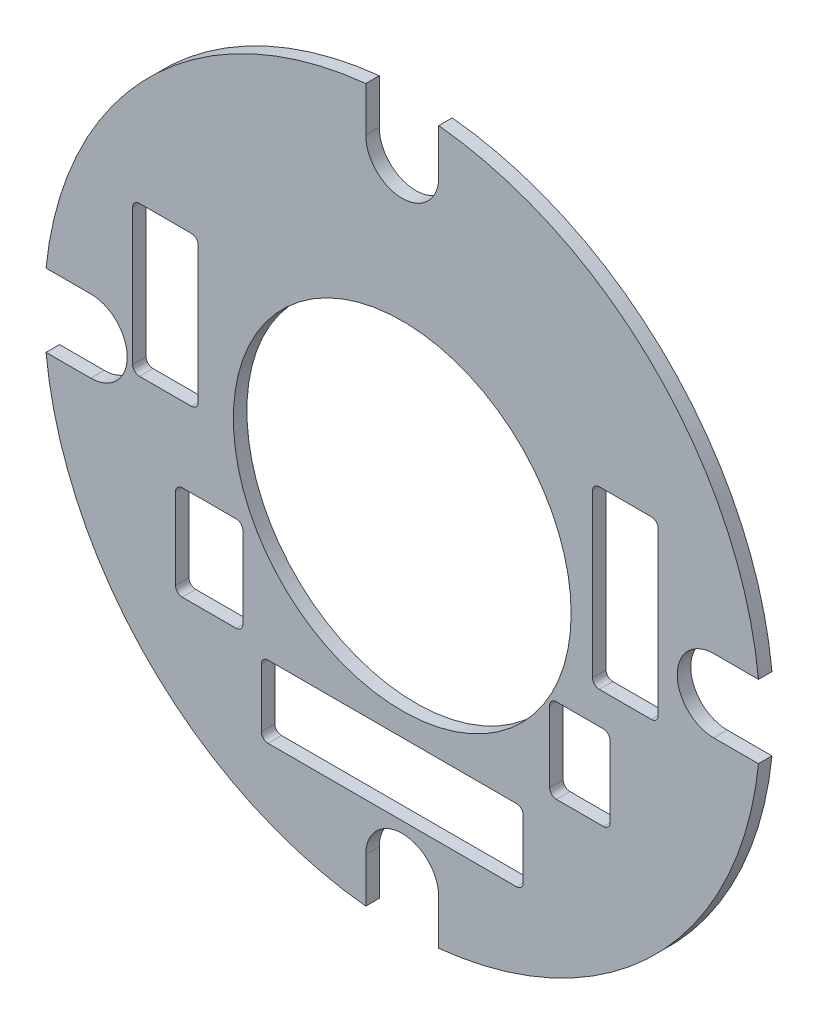
SolidWorks part; units mm, degrees
material "POM 乙缩醛共聚物"
ref_plane "前视基准面" through (0, 0, 0) normal (0, 0, 1) x (1, 0, 0)
ref_plane "上视基准面" through (0, 0, 0) normal (0, 1, 0) x (1, 0, 0)
ref_plane "右视基准面" through (0, 0, 0) normal (1, 0, 0) x (0, 0, -1)
sketch "草图1" plane through (0, 0, 0) normal (0, 0, 1) x (1, 0, 0)
  circle A0 centre (0, 0) radius 12.5
  circle A1 centre (0, 0) radius 26.5
extrude "凸台-拉伸1" add sketch "草图1" along normal blind 1
sketch "草图2" plane through (22.804, -9.3503, -2.5) normal (0, 0, 1) x (1, 0, 0)
  line L0 (-38.402, 19.6523) -> (-42.258, 19.6523)
  line L25 (-42.758, 19.1523) -> (-42.758, 9.0733)
  line L26 (-38.402, 8.5733) -> (-42.258, 8.5733)
  line L27 (-37.902, 19.1523) -> (-37.902, 9.0733)
  line L28 (-8.222, 18.5093) -> (-4.366, 18.5093)
  line L29 (-3.866, 18.0093) -> (-3.866, 6.0253)
  line L30 (-8.222, 5.5253) -> (-4.366, 5.5253)
  line L31 (-8.722, 18.0093) -> (-8.722, 6.0253)
  line L36 (-32.733, -4.8587) -> (-14.352, -4.8587)
  line L37 (-13.852, -5.3587) -> (-13.852, -9.6907)
  line L38 (-32.733, -10.1907) -> (-14.352, -10.1907)
  line L39 (-33.233, -5.3587) -> (-33.233, -9.6907)
  line L40 (-35.1, 3.0153) -> (-39.083, 3.0153)
  line L41 (-39.583, 2.5153) -> (-39.583, -3.4997)
  line L42 (-35.1, -3.9997) -> (-39.083, -3.9997)
  line L43 (-34.6, 2.5153) -> (-34.6, -3.4997)
  line L44 (-11.397, 3.1423) -> (-7.922, 3.1423)
  line L45 (-7.422, 2.6423) -> (-7.422, -2.6107)
  line L46 (-11.397, -3.1107) -> (-7.922, -3.1107)
  line L47 (-11.897, 2.6423) -> (-11.897, -2.6107)
  arc A0 (-38.402, 19.6523) -> (-37.902, 19.1523) centre (-38.402, 19.1523) cw
  arc A1 (-42.258, 19.6523) -> (-42.758, 19.1523) centre (-42.258, 19.1523) ccw
  arc A2 (-42.758, 9.0733) -> (-42.258, 8.5733) centre (-42.258, 9.0733) ccw
  arc A3 (-38.402, 8.5733) -> (-37.902, 9.0733) centre (-38.402, 9.0733) ccw
  arc A4 (-39.583, -3.4997) -> (-39.083, -3.9997) centre (-39.083, -3.4997) ccw
  arc A5 (-39.083, 3.0153) -> (-39.583, 2.5153) centre (-39.083, 2.5153) ccw
  arc A6 (-35.1, 3.0153) -> (-34.6, 2.5153) centre (-35.1, 2.5153) cw
  arc A7 (-35.1, -3.9997) -> (-34.6, -3.4997) centre (-35.1, -3.4997) ccw
  arc A8 (-32.733, -4.8587) -> (-33.233, -5.3587) centre (-32.733, -5.3587) ccw
  arc A9 (-32.733, -10.1907) -> (-33.233, -9.6907) centre (-32.733, -9.6907) cw
  arc A10 (-13.852, -9.6907) -> (-14.352, -10.1907) centre (-14.352, -9.6907) cw
  arc A11 (-14.352, -4.8587) -> (-13.852, -5.3587) centre (-14.352, -5.3587) cw
  arc A12 (-7.422, -2.6107) -> (-7.922, -3.1107) centre (-7.922, -2.6107) cw
  arc A13 (-11.397, -3.1107) -> (-11.897, -2.6107) centre (-11.397, -2.6107) cw
  arc A14 (-11.397, 3.1423) -> (-11.897, 2.6423) centre (-11.397, 2.6423) ccw
  arc A15 (-7.922, 3.1423) -> (-7.422, 2.6423) centre (-7.922, 2.6423) cw
  arc A16 (-3.866, 6.0253) -> (-4.366, 5.5253) centre (-4.366, 6.0253) cw
  arc A17 (-8.222, 5.5253) -> (-8.722, 6.0253) centre (-8.222, 6.0253) cw
  arc A18 (-8.222, 18.5093) -> (-8.722, 18.0093) centre (-8.222, 18.0093) ccw
  arc A19 (-4.366, 18.5093) -> (-3.866, 18.0093) centre (-4.366, 18.0093) cw
  dimension "D1" = 0.5
extrude "切除-拉伸1" cut sketch "草图2" against normal up to next from surface starting at face at (26.5, 0, 1)
sketch "草图3" plane through (22.804, -9.3503, -2.5) normal (0, 0, 1) x (1, 0, 0)
  circle A0 centre (-22.804, 32.4003) radius 1.52
  circle A1 centre (-45.854, 9.3503) radius 1.52
  circle A2 centre (-22.804, -13.6997) radius 1.52
  circle A3 centre (0.246, 9.3503) radius 1.52
extrude "切除-拉伸2" cut sketch "草图3" against normal up to next from surface starting at face at (16.51, 2.667, 1)
sketch "草图4" plane through (0, 0, 0) normal (0, 0, 1) x (1, 0, 0)
  line L0 (-2.7, 23.05) -> (-2.7, 28.1243)
  line L1 (-2.7, 28.1243) -> (2.7, 28.1243)
  line L2 (2.7, 28.1243) -> (2.7, 23.05)
  line L3 (23.05, 2.7) -> (28.1243, 2.7)
  line L4 (28.1243, 2.7) -> (28.1243, -2.7)
  line L5 (28.1243, -2.7) -> (23.05, -2.7)
  line L6 (2.7, -23.05) -> (2.7, -28.1243)
  line L7 (2.7, -28.1243) -> (-2.7, -28.1243)
  line L8 (-2.7, -28.1243) -> (-2.7, -23.05)
  line L9 (-23.05, -2.7) -> (-28.1243, -2.7)
  line L10 (-28.1243, -2.7) -> (-28.1243, 2.7)
  line L11 (-28.1243, 2.7) -> (-23.05, 2.7)
  arc A1 (-2.7, 23.05) -> (2.7, 23.05) centre (0, 23.05) ccw
  arc A2 (23.05, 2.7) -> (23.05, -2.7) centre (23.05, 0) ccw
  arc A3 (2.7, -23.05) -> (-2.7, -23.05) centre (0, -23.05) ccw
  arc A4 (-23.05, -2.7) -> (-23.05, 2.7) centre (-23.05, 0) ccw
  point P27 (0, 0)
  dimension "D1" = 4
extrude "切除-拉伸4" cut sketch "草图4" along normal blind 10
